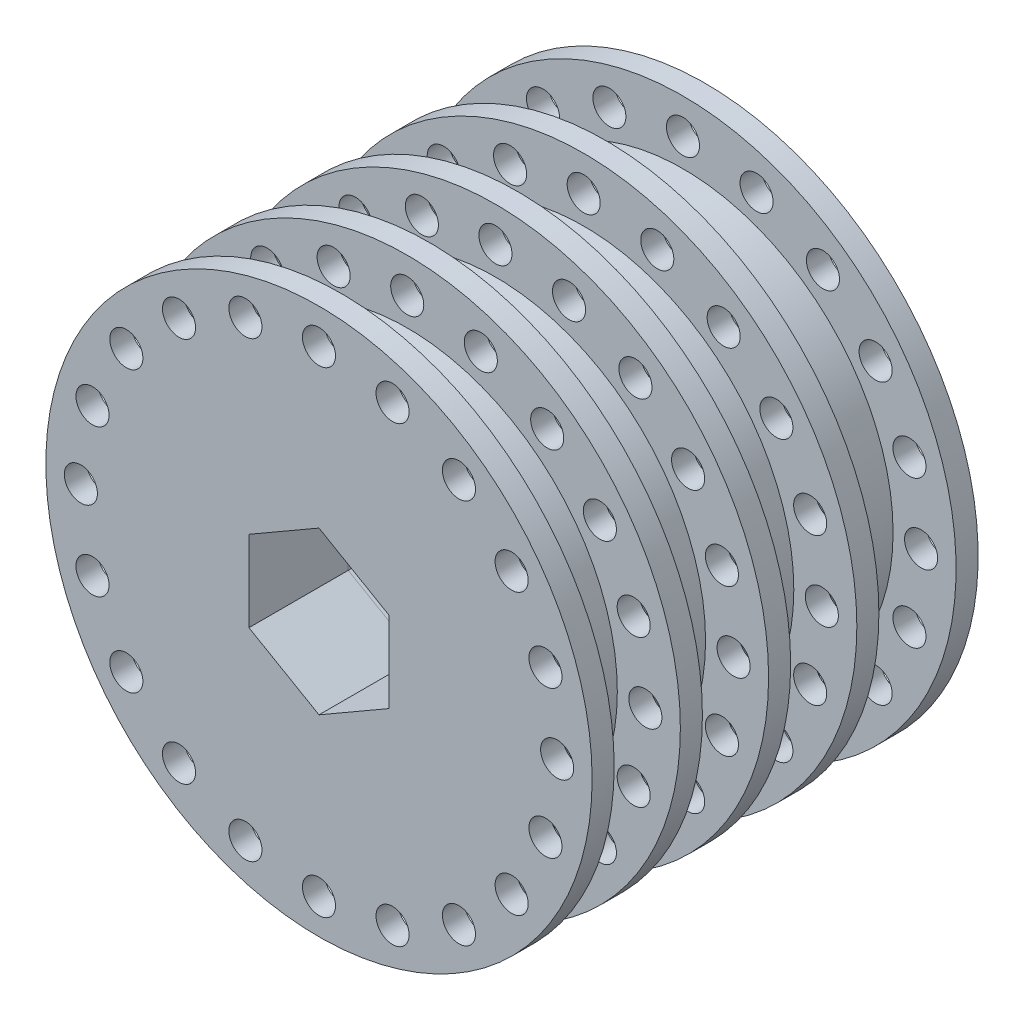
SolidWorks part; units mm, degrees
ref_plane "Front Plane" through (0, 0, 0) normal (0, 0, 1) x (1, 0, 0)
ref_plane "Top Plane" through (0, 0, 0) normal (0, 1, 0) x (1, 0, 0)
ref_plane "Right Plane" through (0, 0, 0) normal (1, 0, 0) x (0, 0, -1)
sketch "Sketch1" plane through (0, 0, 0) normal (0, 0, 1) x (1, 0, 0)
  circle A0 centre (0, 0) radius 19.05
  circle A1 centre (0, 0) radius 24.765
  circle A2 centre (0, 21.59) radius 1.5
  circle A3 centre (6.6717, 20.5333) radius 1.5
  circle A4 centre (12.6903, 17.4667) radius 1.5
  circle A5 centre (17.4667, 12.6903) radius 1.5
  circle A6 centre (20.5333, 6.6717) radius 1.5
  circle A7 centre (21.59, 0) radius 1.5
  circle A8 centre (20.5333, -6.6717) radius 1.5
  circle A9 centre (17.4667, -12.6903) radius 1.5
  circle A10 centre (12.6903, -17.4667) radius 1.5
  circle A11 centre (6.6717, -20.5333) radius 1.5
  circle A12 centre (0, -21.59) radius 1.5
  circle A13 centre (-6.6717, -20.5333) radius 1.5
  circle A14 centre (-12.6903, -17.4667) radius 1.5
  circle A15 centre (-17.4667, -12.6903) radius 1.5
  circle A16 centre (-20.5333, -6.6717) radius 1.5
  circle A17 centre (-21.59, 0) radius 1.5
  circle A18 centre (-20.5333, 6.6717) radius 1.5
  circle A19 centre (-17.4667, 12.6903) radius 1.5
  circle A20 centre (-12.6903, 17.4667) radius 1.5
  circle A21 centre (-6.6717, 20.5333) radius 1.5
  point P47 (0, 0)
  dimension "D1" = 38.1
  dimension "D2" = 49.53
  dimension "D3" = 3
  dimension "D4" = 20
extrude "Boss-Extrude1" add sketch "Sketch1" along normal blind 2 contours A0 | A1 A21 A20 A19 A18 A17 A16 A15 A14 A13 A12 A11 A10 A9 A8 A7 A6 A5 A4 A3 A2 A0 region at (0, 0, 0) region at (-24.0645, 0, 0)
extrude "Boss-Extrude2" add sketch "Sketch1<3>" against normal blind 7 contours A0 region at (0, 0, 0)
sketch "Sketch1<3>" plane through (0, 0, 0) normal (0, 0, 1) x (1, 0, 0) same geometry as "Sketch1"
pattern_linear "LPattern2" count 4 spacing 8 along (0, 0, -1) of "Boss-Extrude2", "Boss-Extrude1"
sketch "Sketch2" plane through (0, 0, -31) normal (0, 0, -1) x (-1, 0, 0)
  circle A1 centre (0, 0) radius 19.05 construction
  circle A2 centre (0, 0) radius 24.765 construction
  circle A3 centre (0, 0) radius 19.05
  circle A4 centre (0, 0) radius 24.765
  circle A5 centre (12.6903, 17.4667) radius 1.5
  circle A6 centre (12.6903, 17.4667) radius 1.5
  circle A7 centre (17.4667, 12.6903) radius 1.5
  circle A8 centre (17.4667, 12.6903) radius 1.5
  circle A9 centre (20.5333, 6.6717) radius 1.5
  circle A10 centre (20.5333, 6.6717) radius 1.5
  circle A11 centre (21.59, 0) radius 1.5
  circle A12 centre (21.59, 0) radius 1.5
  circle A13 centre (20.5333, -6.6717) radius 1.5
  circle A14 centre (20.5333, -6.6717) radius 1.5
  circle A15 centre (17.4667, -12.6903) radius 1.5
  circle A16 centre (17.4667, -12.6903) radius 1.5
  circle A17 centre (12.6903, -17.4667) radius 1.5
  circle A18 centre (12.6903, -17.4667) radius 1.5
  circle A19 centre (6.6717, -20.5333) radius 1.5
  circle A20 centre (6.6717, -20.5333) radius 1.5
  circle A21 centre (0, -21.59) radius 1.5
  circle A22 centre (0, -21.59) radius 1.5
  circle A23 centre (-6.6717, -20.5333) radius 1.5
  circle A24 centre (-6.6717, -20.5333) radius 1.5
  circle A25 centre (-12.6903, -17.4667) radius 1.5
  circle A26 centre (-12.6903, -17.4667) radius 1.5
  circle A27 centre (-17.4667, -12.6903) radius 1.5
  circle A28 centre (-17.4667, -12.6903) radius 1.5
  circle A29 centre (-20.5333, -6.6717) radius 1.5
  circle A30 centre (-20.5333, -6.6717) radius 1.5
  circle A31 centre (-21.59, 0) radius 1.5
  circle A32 centre (-21.59, 0) radius 1.5
  circle A33 centre (-20.5333, 6.6717) radius 1.5
  circle A34 centre (-20.5333, 6.6717) radius 1.5
  circle A35 centre (-17.4667, 12.6903) radius 1.5
  circle A36 centre (-17.4667, 12.6903) radius 1.5
  circle A37 centre (-12.6903, 17.4667) radius 1.5
  circle A38 centre (-12.6903, 17.4667) radius 1.5
  circle A39 centre (-6.6717, 20.5333) radius 1.5
  circle A40 centre (-6.6717, 20.5333) radius 1.5
  circle A41 centre (0, 21.59) radius 1.5
  circle A42 centre (0, 21.59) radius 1.5
  circle A43 centre (0, 0) radius 19.05
  circle A44 centre (0, 0) radius 19.05
  circle A45 centre (6.6717, 20.5333) radius 1.5
  circle A46 centre (6.6717, 20.5333) radius 1.5
  circle M22 centre (0, 0) radius 19.05
  dimension "D1" = 0
  dimension "D2" = 0
  dimension "D3" = 0
  dimension "D4" = 0
  dimension "D5" = 0
  dimension "D6" = 0
  dimension "D7" = 0
  dimension "D8" = 0
  dimension "D9" = 0
  dimension "D10" = 0
  dimension "D11" = 0
  dimension "D12" = 0
  dimension "D13" = 0
  dimension "D14" = 0
  dimension "D15" = 0
  dimension "D16" = 0
  dimension "D17" = 0
  dimension "D18" = 0
  dimension "D19" = 0
  dimension "D20" = 0
  dimension "D21" = 0
extrude "Boss-Extrude3" add sketch "Sketch2" along normal blind 2 contours A4 A46 A42 A40 A38 A36 A34 A32 A30 A28 A26 A24 A22 A20 A18 A16 A14 A12 A10 A8 A6 M22 | M22 region at (0, 0, -31) region at (24.0645, 0, -31)
sketch "Sketch3" plane through (0, 0, -33) normal (0, 0, -1) x (-1, 0, 0)
  line L1 (0, 7.3323) -> (-6.35, 3.6662)
  line L2 (-6.35, 3.6662) -> (-6.35, -3.6662)
  line L3 (-6.35, -3.6662) -> (0, -7.3323)
  line L4 (0, -7.3323) -> (6.35, -3.6662)
  line L5 (6.35, -3.6662) -> (6.35, 3.6662)
  line L6 (6.35, 3.6662) -> (0, 7.3323)
  circle A0 centre (0, 0) radius 6.35 construction
  circle A2 centre (0, 0) radius 19.05
  dimension "D2" = 38.1
extrude "Cut-Extrude1" cut sketch "Sketch3" against normal through all contours L5 L6 L1 L2 L3 L4 region at (0, 0, -33)
